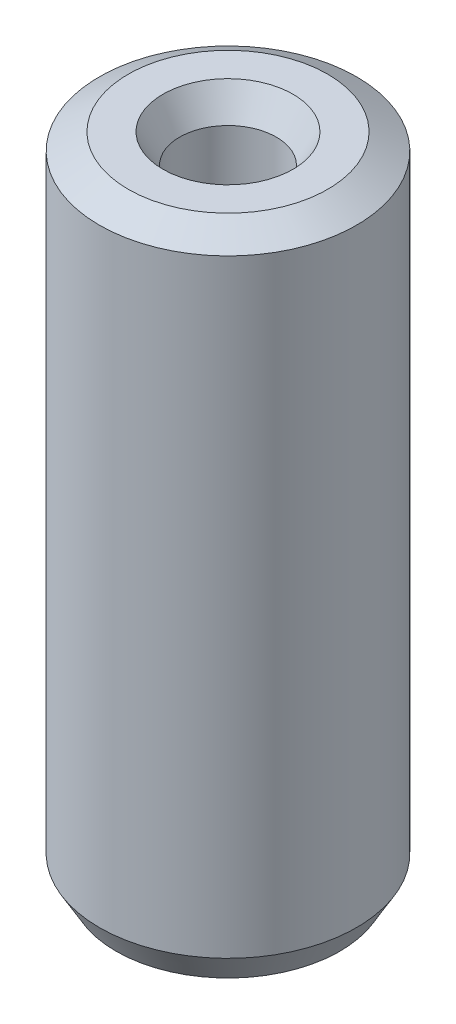
SolidWorks part; units mm, degrees
ref_plane "Front Plane" through (0, 0, 0) normal (0, 0, 1) x (1, 0, 0)
ref_plane "Top Plane" through (0, 0, 0) normal (0, 1, 0) x (1, 0, 0)
ref_plane "Right Plane" through (0, 0, 0) normal (1, 0, 0) x (0, 0, -1)
sketch "Sketch1" plane through (0, 0, 0) normal (0, 1, 0) x (1, 0, 0)
  circle A0 centre (0, 0) radius 30
  dimension "SLEEVE_OD" = 60
extrude "Boss-Extrude1" add sketch "Sketch1" along normal blind 152.5307
sketch "Sketch2" plane through (0, 0, 0) normal (0, 1, 0) x (1, 0, 0)
  circle A0 centre (0, 0) radius 11.294
  dimension "BORE_D" = 22.5881
extrude "Cut-Extrude1" cut sketch "Sketch2" along normal through all
chamfer "Chamfer1" distance 3.8839 angle 60 4 edges at (0, 152.5307, 11.294) (0, 0, 11.294) (0, 0, 30) (0, 152.5307, 30) first distance on face at (0, 152.5307, 11.294) first distance on face at (0, 0, 11.294) first distance on face at (0, 152.5307, 30)
